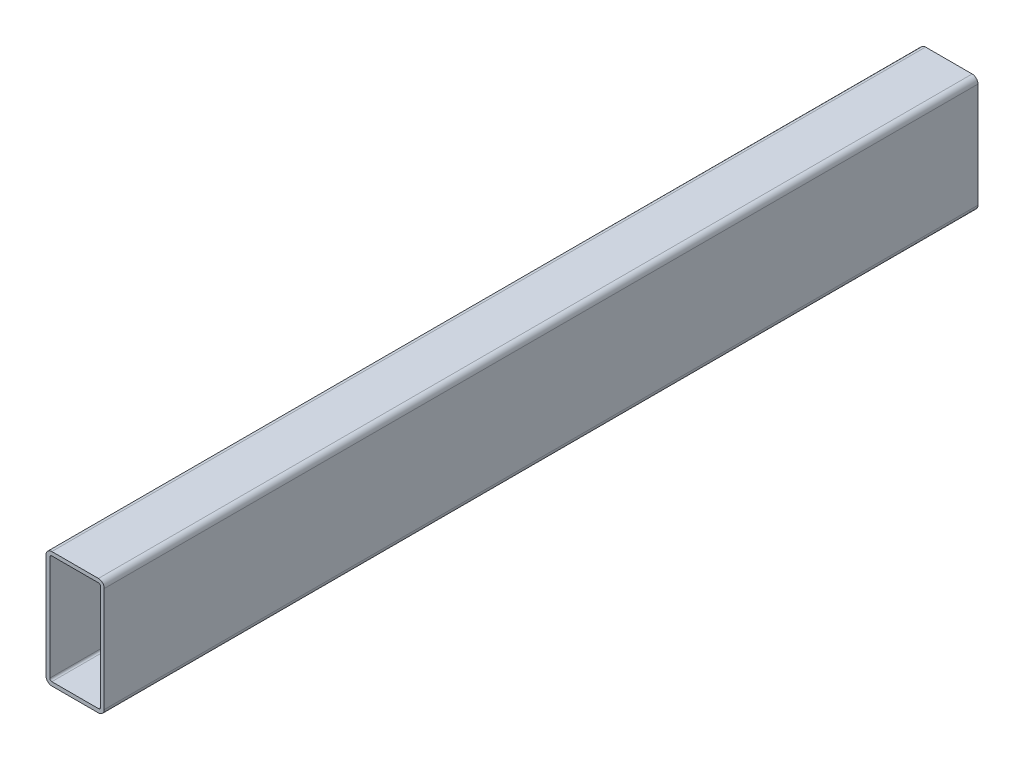
SolidWorks part; units mm, degrees
ref_plane "Front Plane" through (0, 0, 0) normal (0, 0, 1) x (1, 0, 0)
ref_plane "Top Plane" through (0, 0, 0) normal (0, 1, 0) x (1, 0, 0)
ref_plane "Right Plane" through (0, 0, 0) normal (1, 0, 0) x (0, 0, -1)
sketch "Sketch1" plane through (0, 0, 0) normal (0, 0, 1) x (1, 0, 0)
  line L1 (10.16, -25.4) -> (-10.16, -25.4)
  line L2 (12.7, -22.86) -> (12.7, 22.86)
  line L3 (10.16, 25.4) -> (-10.16, 25.4)
  line L4 (-12.7, -22.86) -> (-12.7, 22.86)
  line L5 (12.7, -25.4) -> (-12.7, 25.4) construction
  line L6 (12.7, 25.4) -> (-12.7, -25.4) construction
  arc A0 (-10.16, -25.4) -> (-12.7, -22.86) centre (-10.16, -22.86) cw
  arc A1 (10.16, -25.4) -> (12.7, -22.86) centre (10.16, -22.86) ccw
  arc A2 (12.7, 22.86) -> (10.16, 25.4) centre (10.16, 22.86) ccw
  arc A3 (-10.16, 25.4) -> (-12.7, 22.86) centre (-10.16, 22.86) ccw
  point P0 (0, 0)
  dimension "D3" = 2.54
  dimension "D1" = 25.4
  dimension "D2" = 50.8
extrude "Extrude-Thin1" add sketch "Sketch1" along normal blind 381 thin thin type one direction reverse wall 1.651
